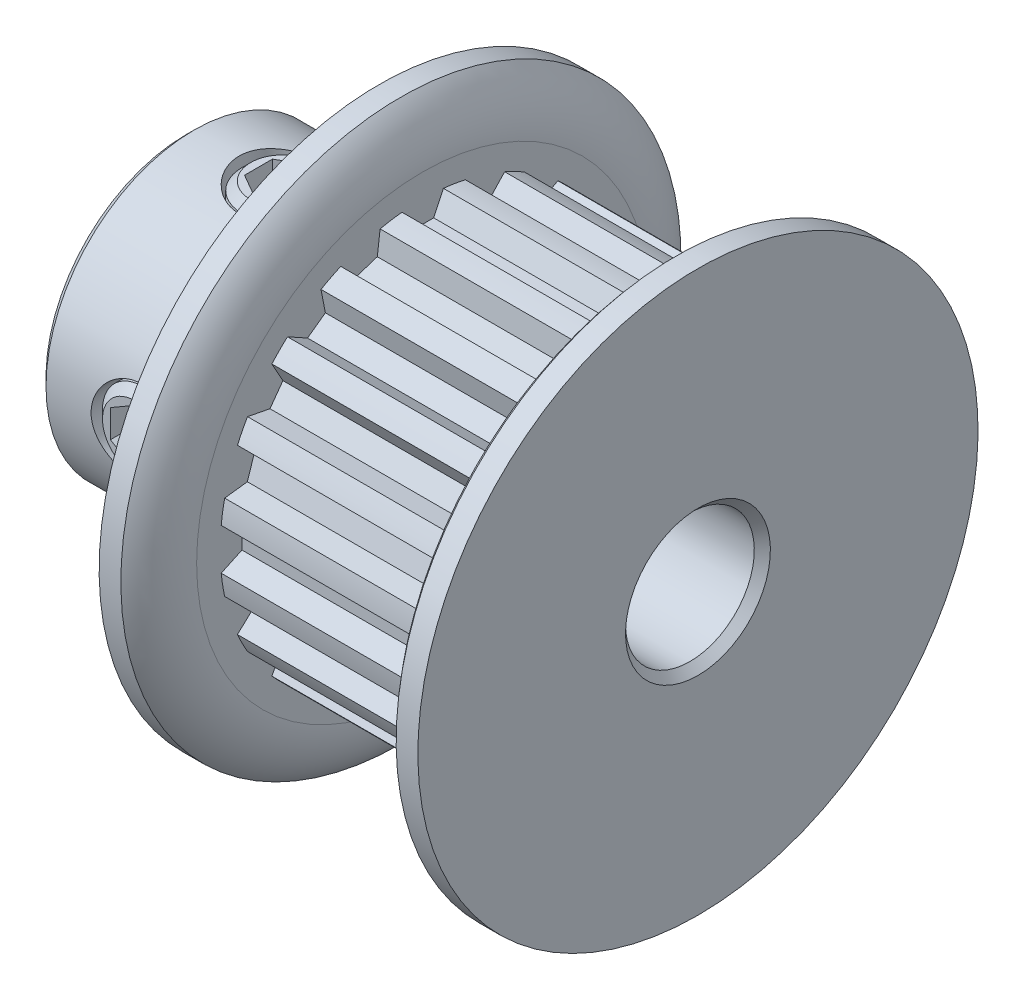
SolidWorks part; units mm, degrees
ref_plane "Front Plane" through (0, 0, 0) normal (0, 0, 1) x (1, 0, 0)
ref_plane "Top Plane" through (0, 0, 0) normal (0, 1, 0) x (1, 0, 0)
ref_plane "Right Plane" through (0, 0, 0) normal (1, 0, 0) x (0, 0, -1)
sketch "Sketch2" plane through (0, 0, 0) normal (1, 0, 0) x (0, 0, -1)
  line L3 (0, 0) -> (0, 5.6245) construction
  line L6 (0, -6.1325) -> (0, -6.45) construction
  line L7 (-0.5715, 6.1058) -> (-0.3422, 5.6141)
  line L8 (0.5715, 6.1058) -> (0.3422, 5.6141)
  line L9 (-0.5715, 6.1058) -> (-0.6426, 6.2583)
  line L10 (0.5715, 6.1058) -> (0.6426, 6.2583)
  line L12 (-0.3422, 5.6141) -> (0.3422, 5.6141)
  line L14 (0, 6.1325) -> (0, 6.45) construction
  line L15 (0, 0) -> (0, -1.143) construction
  circle A0 centre (0, 0) radius 6.45 construction
  circle A1 centre (0, 0) radius 5.6245 construction
  circle A2 centre (0, 0) radius 6.1325 construction
  arc A7 (0.6426, 6.2583) -> (-0.6426, 6.2583) centre (0, 0) ccw
  point P5 (0, 6.2913)
  dimension "D3" = 0.3175
  dimension "D1" = 50
sketch "Sketch1" plane through (0, 0, 0) normal (0, 0, 1) x (1, 0, 0)
  line L0 (-7.95, 0) -> (7.95, 0) construction
  line L1 (-7.95, 2) -> (7.95, 2)
  line L2 (-7.95, 2) -> (-7.95, 4.6)
  line L3 (-1.95, 8.7) -> (-1.275, 8.7)
  line L4 (-0.6, 6.45) -> (-0.6, 7.0215)
  line L5 (-0.6, 7.593) -> (-0.6, 6.45) construction
  line L6 (-0.6, 6.45) -> (6.6, 6.45)
  line L7 (6.6, 6.45) -> (6.6, 7.0215)
  line L8 (6.6, 6.45) -> (7.95, 6.45) construction
  line L9 (7.275, 8.7) -> (7.95, 8.7)
  line L10 (7.95, 8.7) -> (7.95, 2)
  line L11 (7.275, 6.45) -> (7.275, 8.7) construction
  line L12 (-4.95, 4.6) -> (-4.95, 2) construction
  line L13 (-1.95, 8.7) -> (-1.95, 4.6)
  line L14 (-1.95, 4.6) -> (-7.95, 4.6)
  arc A0 (6.6, 7.0215) -> (7.275, 8.7) centre (9.0244, 7.0215) cw
  arc A1 (-0.6, 7.0215) -> (-1.275, 8.7) centre (-3.0244, 7.0215) ccw
  dimension "Bore Size" = 4
  dimension "Overall Width" = 15.9
  dimension "Inside Width" = 7.2
  dimension "OD" = 17.4
  dimension "D2" = 12.9
  dimension "D3" = 1.143
  dimension "D4" = 0.5715
  dimension "Outside Width" = 9.9
revolve "Revolve1" add sketch "Sketch1" angle 360 mid plane about L0
sketch "Sketch4" plane through (-0.6, 0, 0) normal (1, 0, 0) x (0, 0, -1)
  circle A0 centre (0, 0) radius 6.2913
  circle A2 centre (0, 0) radius 6.45
  circle A3 centre (0, 0) radius 6.45 construction
extrude "Cut-Extrude2" cut sketch "Sketch4" along normal up to surface (7.2 mm away) up to face at (6.6, -6.45, 0)
sketch "Sketch3" plane through (-0.6, 0, 0) normal (1, 0, 0) x (0, 0, -1)
  line L2 (-0.5715, 6.1058) -> (-0.3422, 5.6141) construction
  line L3 (-0.3422, 5.6141) -> (0.3422, 5.6141) construction
  line L4 (0.5715, 6.1058) -> (0.3422, 5.6141) construction
  line L5 (-0.6426, 6.2583) -> (-0.3422, 5.6141)
  line L6 (-0.3422, 5.6141) -> (0.3422, 5.6141)
  line L7 (0.6426, 6.2583) -> (0.3422, 5.6141)
  arc A1 (0.6426, 6.2583) -> (-0.6426, 6.2583) centre (0, 0) ccw construction
  arc A2 (0.6426, 6.2583) -> (-0.6426, 6.2583) centre (0, 0) ccw
extrude "Cut-Extrude1" cut sketch "Sketch3" along normal up to surface (7.2 mm away)
pattern_circular "CirPattern1" count 20 over 360 of "Cut-Extrude1"
sketch "Sketch5" plane through (0, 0, 0) normal (0, 0, 1) x (1, 0, 0)
  line L1 (6.6, 7.0215) -> (6.6, -7.0215) construction
  point P0 (6.6, 0)
sketch "Sketch6" plane through (0, 0, 0) normal (0, 1, 0) x (1, 0, 0)
  line L0 (-7.95, 0) -> (-6.2, 0) construction
  line L1 (-7.95, 8.7) -> (-7.95, -8.7) construction
  line L2 (-1.95, 0) -> (-3.7, 0) construction
  line L4 (-1.95, 8.7) -> (-1.95, -8.7) construction
  circle A0 centre (-4.95, 0) radius 1.25 construction
  circle A1 centre (-4.95, 0) radius 1.35
  dimension "D1" = 0.1
  dimension "SS Dia" = 2.5
extrude "Cut-Extrude3" cut sketch "Sketch6" along normal through all
sketch "Sketch7" plane through (0, 0, 0) normal (0, 0, 1) x (1, 0, 0)
  line L0 (-5.946, 4.6) -> (-4.95, 4.6)
  line L1 (-6.2, 4.346) -> (-6.2, 2.635)
  line L2 (-6.2, 2.635) -> (-5.946, 2.381)
  line L3 (-5.946, 2.381) -> (-4.95, 2.381)
  line L4 (-4.95, 2.381) -> (-4.95, 4.6) construction
  line L5 (-1.95, 4.6) -> (-7.95, 4.6) construction
  line L6 (-6.2, 4.346) -> (-5.946, 4.6)
  line L8 (-4.95, 4.6) -> (-4.95, 2.381)
  point P0 (-6.2, 4.6)
  point P4 (-6.2, 2.381)
  dimension "D2" = 0.381
revolve "Revolve2" add sketch "Sketch7" angle 360 mid plane about L4
sketch "Sketch8" plane through (0, 4.6, 0) normal (0, 1, 0) x (1, 0, 0)
  line L1 (-4.95, 0.866) -> (-5.7, 0.433)
  line L2 (-5.7, 0.433) -> (-5.7, -0.433)
  line L3 (-5.7, -0.433) -> (-4.95, -0.866)
  line L4 (-4.95, -0.866) -> (-4.2, -0.433)
  line L5 (-4.2, -0.433) -> (-4.2, 0.433)
  line L6 (-4.2, 0.433) -> (-4.95, 0.866)
  circle A0 centre (-4.95, 0) radius 0.75 construction
  dimension "D1" = 1.5
extrude "Cut-Extrude4" cut sketch "Sketch8" against normal blind 1.016
pattern_circular "CirPattern2" count 2 over 90 about axis through (-7.95, 0, 0) along (-1, 0, 0) of "Cut-Extrude3" reverse direction yes
pattern_circular "CirPattern3" count 2 over 90 reverse direction yes of bodies 107
chamfer "Chamfer1" distance 0.25 angle 45 3 edges at (-7.95, -4.6, 0) (7.95, -2, 0) (-7.95, -2, 0)
ref_axis "Center Axis 1" through (7.7, 0, 0) along (-1, 0, 0)
ref_plane "Contact Plane 1" through (-7.95, 0, 0) normal (-1, 0, 0) x (0, 0, 1)
ref_plane "Contact Plane 2" through (7.95, 0, 0) normal (1, 0, 0) x (0, 0, -1)
equation "\"D3@Sketch2\" = (\"hs@Sketch2\"-\"ht@Sketch2\")/2"
equation "\"D2@Sketch1\" = \"PD@Sketch2\""
equation "\"D3@Sketch1\" = \"hs@Sketch2\""
equation "\"D4@Sketch1\" = \"D3@Sketch1\"/2"
